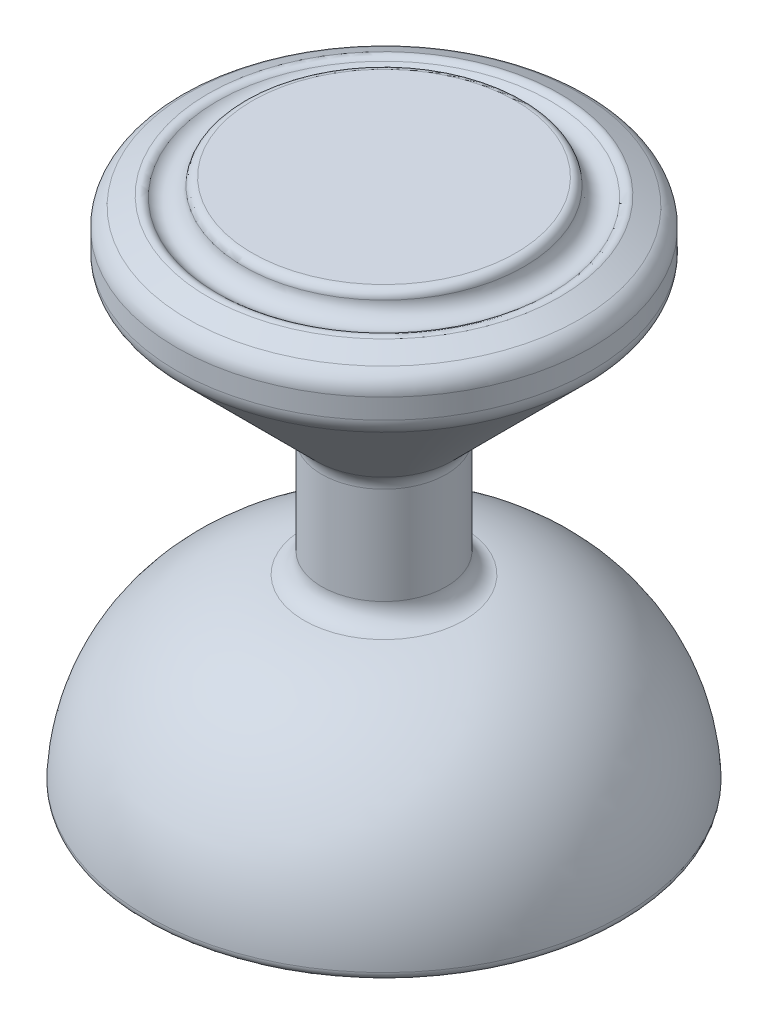
SolidWorks part; units mm, degrees
ref_plane "前视基准面" through (0, 0, 0) normal (0, 0, 1) x (1, 0, 0)
ref_plane "上视基准面" through (0, 0, 0) normal (0, 1, 0) x (1, 0, 0)
ref_plane "右视基准面" through (0, 0, 0) normal (1, 0, 0) x (0, 0, -1)
other "Configuration Table"
ref_axis "基准轴1" through (0, -25.6995, 0) along (0, 1, 0)
sketch "草图1" plane through (0, 0, 0) normal (0, 0, 1) x (1, 0, 0)
  line L0 (0, 0) -> (0, 7.6196) construction
  line L1 (0, -25.6995) -> (0, 39.9139) construction
  line L2 (0, 7.6196) -> (0, 25.5)
  line L3 (0, 25.5) -> (89.9085, 25.5) construction
  line L4 (10.5, 0) -> (11.5, 0)
  line L5 (3, 9) -> (3, 15)
  line L6 (3, 9) -> (0, 9) construction
  line L7 (7.799, 6) -> (0, 6)
  line L8 (0, 6) -> (0, 7.6196)
  line L9 (10, 22) -> (10, 24)
  line L10 (10, 23) -> (0, 23) construction
  line L11 (6.8189, 25.5) -> (8.1811, 24.872) construction
  line L12 (10, 22) -> (3, 15)
  line L13 (11.5, 0) -> (11.5, 10.5266) construction
  line L14 (6.8189, 25.5) -> (0, 25.5)
  arc A1 (3, 9) -> (11.5, 0) centre (2.4853, 0) cw
  arc A8 (6.8189, 25.5) -> (8.1811, 24.872) centre (7.5, 25.186) ccw
  arc A9 (8.1811, 24.872) -> (10, 24) centre (-19.8579, -35.9475) cw
  arc A11 (7.799, 6) -> (10.5, 0) centre (2.4853, 0) cw
  point P13 (11, 0)
  dimension "D6" = 1.5
  dimension "D1" = 9
  dimension "D2" = 3
  dimension "D3" = 11.5
  dimension "D4" = 1
  dimension "D5" = 6
  dimension "D7" = 6
  dimension "D8" = 2
  dimension "D9" = 10
  dimension "D11" = 45
  dimension "D13" = 2.5
  dimension "D15" = 1.5
revolve "旋转1" add sketch "草图1" angle 360 about L0 region at (3.928, 16.3272, 0)
sketch "草图2" plane through (0, 6, 0) normal (0, -1, 0) x (1, 0, 0)
  line L1 (-1.05, 0.6) -> (1.05, 0.6)
  line L2 (-1.05, 0.6) -> (-1.05, -0.6)
  line L3 (-1.05, -0.6) -> (1.05, -0.6)
  line L4 (1.05, 0.6) -> (1.05, -0.6)
  line L5 (-1.05, 0.6) -> (1.05, -0.6) construction
  line L6 (-1.05, -0.6) -> (1.05, 0.6) construction
  point P0 (0, 0)
  dimension "D1" = 2.1
  dimension "D2" = 1.2
extrude "切除-拉伸1" cut sketch "草图2" against normal blind 3.8
fillet "圆角1" radius 0.4 5 edges at (11.5, 0, 0) (8.1811, 24.872, 0) (6.8189, 25.5, 0) (10.5, 0, 0) (7.799, 6, 0)
fillet "圆角2" radius 1 4 edges at (10, 22, 0) (10, 24, 0) (3, 9, 0) (3, 15, 0)
fillet "圆角3" radius 0.2 4 edges at (-1.05, 6, 0) (0, 6, -0.6) (0, 6, 0.6) (1.05, 6, 0)
